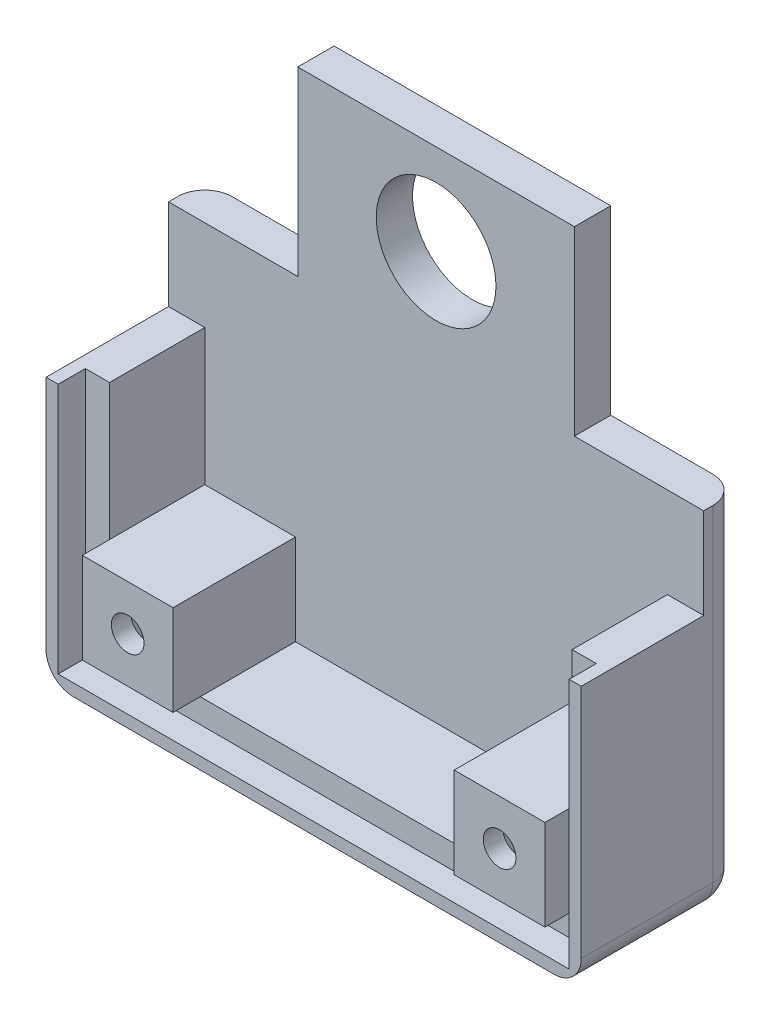
SolidWorks part; units mm, degrees
ref_plane "Płaszczyzna przednia" through (0, 0, 0) normal (0, 0, 1) x (1, 0, 0)
ref_plane "Płaszczyzna górna" through (0, 0, 0) normal (0, 1, 0) x (1, 0, 0)
ref_plane "Płaszczyzna prawa" through (0, 0, 0) normal (1, 0, 0) x (0, 0, -1)
sketch "Sketch1" plane through (0, 0, 0) normal (0, 0, 1) x (1, 0, 0)
  line L1 (-15.25, -10) -> (15.25, -10)
  line L2 (-15.25, -10) -> (-15.25, 10)
  line L3 (-15.25, 10) -> (15.25, 10)
  line L4 (15.25, -10) -> (15.25, 10)
  line L5 (-15.25, -10) -> (15.25, 10) construction
  line L6 (-15.25, 10) -> (15.25, -10) construction
  circle A0 centre (0, 0) radius 6.6
  point P0 (0, 0)
  dimension "D1" = 30.5
  dimension "D2" = 20
extrude "Boss-Extrude1" add sketch "Sketch1" along normal blind 4
sketch "Sketch2" plane through (0, -10, 0) normal (0, -1, 0) x (1, 0, 0)
  line L0 (-15.25, 4) -> (15.25, 0) construction
  line L1 (15.25, 0) -> (15.25, 4) construction
  line L2 (15.25, 4) -> (-15.25, 0) construction
  line L3 (-15.25, 0) -> (-15.25, 4) construction
  line L5 (-29.5, 0) -> (29.5, 0)
  line L6 (-29.5, 0) -> (-29.5, 4)
  line L7 (-29.5, 4) -> (29.5, 4)
  line L8 (29.5, 0) -> (29.5, 4)
  line L9 (-29.5, 0) -> (29.5, 4) construction
  line L10 (-29.5, 4) -> (29.5, 0) construction
  point P6 (0, 2)
  dimension "D1" = 59
extrude "Boss-Extrude2" add sketch "Sketch2" along normal blind 35
sketch "Sketch4" plane through (0, -45, 0) normal (0, -1, 0) x (1, 0, 0)
  line L1 (-29.5, 4) -> (29.5, 4)
  line L2 (-29.5, 4) -> (-29.5, 0)
  line L3 (-29.5, 0) -> (29.5, 0)
  line L4 (29.5, 4) -> (29.5, 0)
extrude "Boss-Extrude3" add sketch "Sketch4" along normal blind 4
sketch "Sketch5" plane through (0, 0, 4) normal (0, 0, 1) x (1, 0, 0)
  line L0 (29.5, -49) -> (29.5, -10) construction
  line L1 (-29.5, -49) -> (29.5, -49)
  line L2 (-29.5, -49) -> (-29.5, -45)
  line L3 (-29.5, -45) -> (29.5, -45)
  line L4 (29.5, -49) -> (29.5, -45)
  line L6 (-29.5, -45) -> (-25.5, -45)
  line L7 (-29.5, -45) -> (-29.5, -20)
  line L8 (-29.5, -20) -> (-25.5, -20)
  line L9 (-25.5, -45) -> (-25.5, -20)
  line L10 (29.5, -45) -> (25.5, -45)
  line L11 (29.5, -45) -> (29.5, -20)
  line L12 (29.5, -20) -> (25.5, -20)
  line L13 (25.5, -45) -> (25.5, -20)
  line M5 (-29.5, -10) -> (-29.5, -49)
  line M6 (-29.5, -49) -> (29.5, -49)
  line M7 (29.5, -49) -> (29.5, -10)
  dimension "D1" = 4
  dimension "D2" = 4
  dimension "D3" = 25
  dimension "D4" = 4
  dimension "D5" = 25
extrude "Boss-Extrude4" add sketch "Sketch5" along normal blind 13.5 contours L3 L9 L8 M5 | L3 M5 M6 M7 | L13 L3 L12 M7 region at (0, -47, 4) region at (-27.5, -32.5, 4) region at (27.5, -32.5, 4)
sketch "Sketch6" plane through (0, 0, 17.5) normal (0, 0, 1) x (1, 0, 0)
  line L0 (-29.5, -20) -> (-25.5, -20) construction
  line L1 (-28.1667, -20) -> (-25.5, -20)
  line L2 (-28.1667, -20) -> (-28.1667, -47.6667)
  line L3 (-28.1667, -47.6667) -> (-25.5, -47.6667)
  line L4 (-25.5, -20) -> (-25.5, -47.6667)
  line L5 (-29.5, -20) -> (-29.5, -49) construction
  line L6 (-29.5, -49) -> (29.5, -49) construction
  line L7 (29.5, -49) -> (29.5, -20) construction
  line L8 (-25.5, -47.6667) -> (28.1667, -47.6667)
  line L9 (-25.5, -47.6667) -> (-25.5, -45)
  line L10 (-25.5, -45) -> (28.1667, -45)
  line L11 (28.1667, -47.6667) -> (28.1667, -45)
  line L12 (29.5, -20) -> (25.5, -20) construction
  line L13 (28.1667, -45) -> (25.5, -45)
  line L14 (28.1667, -45) -> (28.1667, -20)
  line L15 (28.1667, -20) -> (25.5, -20)
  line L16 (25.5, -45) -> (25.5, -20)
  line M9 (29.5, -20) -> (25.5, -20)
  line M13 (-25.5, -20) -> (-29.5, -20)
  dimension "D1" = 1.3333
  dimension "D2" = 2.6667
  dimension "D3" = 1.3333
  dimension "D4" = 1.3333
  dimension "D5" = 2.6667
  dimension "D6" = 2.6667
extrude "Cut-Extrude1" cut sketch "Sketch6" against normal blind 3 contours L4 L2 L3 M13 | L8 L11 L10 L4 | L16 L10 L14 M9 region at (-26.8333, -33.8333, 17.5) region at (1.3333, -46.3333, 17.5) region at (26.8333, -32.5, 17.5)
sketch "Sketch8" plane through (0, 0, 4) normal (0, 0, 1) x (1, 0, 0)
  line L1 (-25.5, -45) -> (-15.5, -45)
  line L2 (-25.5, -45) -> (-25.5, -35)
  line L3 (-25.5, -35) -> (-15.5, -35)
  line L4 (-15.5, -45) -> (-15.5, -35)
  line L5 (25.5, -45) -> (15.5, -45)
  line L6 (25.5, -45) -> (25.5, -35)
  line L7 (25.5, -35) -> (15.5, -35)
  line L8 (15.5, -45) -> (15.5, -35)
  dimension "D1" = 10
  dimension "D2" = 10
  dimension "D3" = 10
  dimension "D4" = 10
extrude "Boss-Extrude5" add sketch "Sketch8" along normal blind 13.5
sketch "Sketch9" plane through (0, 0, 17.5) normal (0, 0, 1) x (1, 0, 0)
  line L0 (-25.5, -35) -> (-15.5, -45) construction
  line L1 (-15.5, -45) -> (-20.5, -40) construction
  line L2 (25.5, -35) -> (15.5, -45) construction
  line L3 (15.5, -45) -> (20.5, -40) construction
  line L4 (-15.5, -35) -> (-25.5, -35) construction
  line L5 (-25.5, -35) -> (-25.5, -45) construction
  line L6 (15.5, -45) -> (25.5, -45) construction
  circle A0 centre (-20.5, -40) radius 1.8
  circle A1 centre (20.5, -40) radius 1.8
  point P12 (-25.5, -35)
  point P13 (-15.5, -45)
  point P15 (-25.5, -35)
  point P20 (25.5, -35)
  point P22 (0, 0)
  point P23 (15.5, -45)
extrude "Cut-Extrude2" cut sketch "Sketch9" against normal blind 20
sketch "Sketch15" plane through (0, 0, 0) normal (0, 0, -1) x (-1, 0, 0)
  circle A0 centre (-20.5, -40) radius 4
  circle A1 centre (20.5, -40) radius 4
extrude "Cut-Extrude3" cut sketch "Sketch15" against normal blind 14
sketch "Sketch18" plane through (0, 0, 14) normal (0, 0, -1) x (-1, 0, 0)
  point P0 (-20.5, -40)
  point P3 (20.5, -40)
hole_wizard "CSK for M3 Countersunk Flat Head Screw2" positions "Sketch18" profile "Sketch17" countersink size "M3" standard "ISO" end condition through all
sketch "Sketch17" plane through (20.5, -40, 14) normal (1, 0, 0) x (0, 1, 0)
  line L0 (0, 0) -> (0, 3.5)
  line L1 (0, 3.5) -> (1.6, 3.5)
  line L2 (1.6, 3.5) -> (1.6, 1.55)
  line L3 (1.6, 1.55) -> (3.15, 0)
  line L5 (3.15, 0) -> (0, 0)
  line L6 (-1.6, 1.55) -> (-3.15, 0) construction
  line L11 (0, -6.35) -> (0, 107.95) construction
  dimension "Thru Hole Dia." = 3.2
  dimension "Thru Hole Depth" = 3.5
  dimension "Near C'Sink Dia." = 6.3
  dimension "Near C'Sink Angle" = 90
fillet "Fillet1" radius 3 3 edges at (29.5, -29.5, 0) (0, -49, 0) (-29.5, -29.5, 0) type face fillet first side face at (16.5, -40, 0) second side face at (-29.5, -26.3333, 7.1667) second side face at (0, -49, 8.75) second side face at (29.5, -26.3333, 7.1667)
fillet "Fillet2" radius 3 1 edges at (29.5, -49, 10.25) type face fillet first side face at (29.5, -26.3333, 8.1667) second side face at (-29.5, -26.3333, 8.1667) second side face at (0, -49, 10.25)
fillet "Fillet3" radius 3 1 edges at (-29.5, -49, 10.25) type face fillet first side face at (-29.5, -26.3333, 8.1667) second side face at (-1.5, -49, 10.25)
